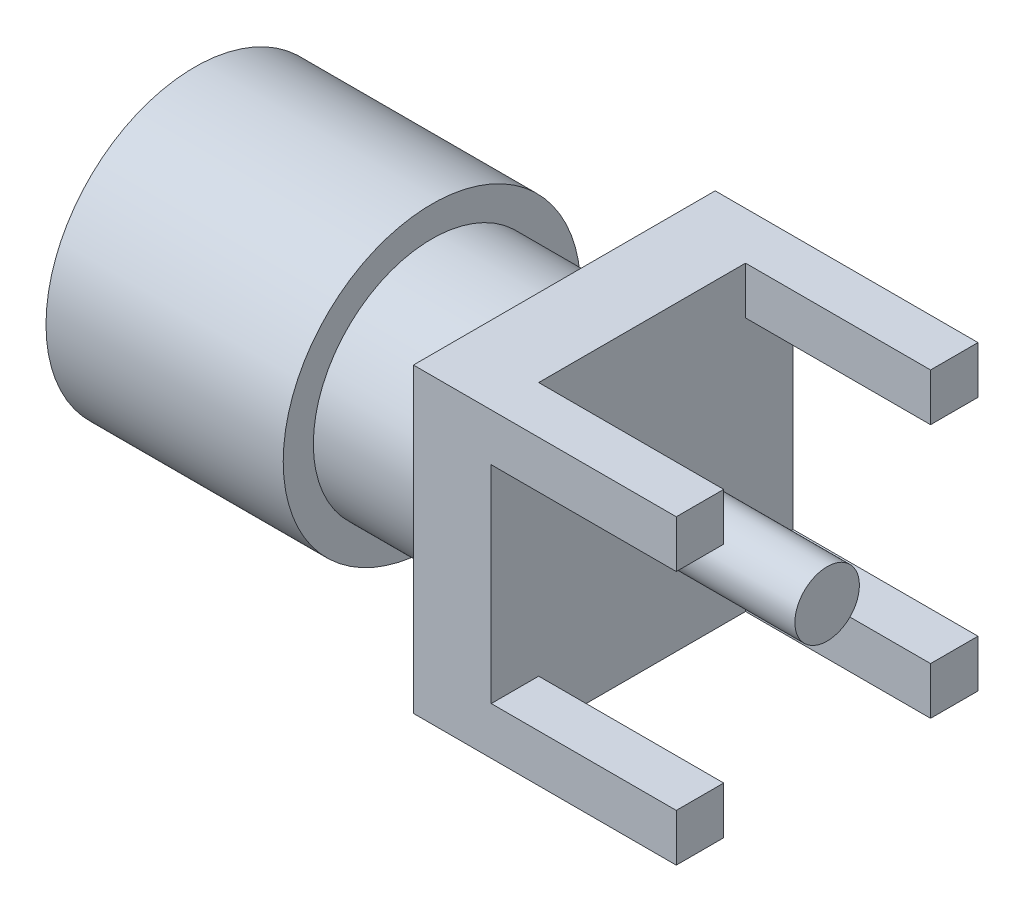
SolidWorks part; units mm, degrees
ref_plane "Front Plane" through (0, 0, 0) normal (0, 0, 1) x (1, 0, 0)
ref_plane "Top Plane" through (0, 0, 0) normal (0, 1, 0) x (1, 0, 0)
ref_plane "Right Plane" through (0, 0, 0) normal (1, 0, 0) x (0, 0, -1)
sketch "Sketch1" plane through (0, 0, 0) normal (0, 0, 1) x (1, 0, 0)
  line L0 (0, 54.8541) -> (0, -52.7238) construction
  line L1 (0, 0) -> (83.3995, 0) construction
  line L3 (-0.82, 3.18) -> (0.82, 3.18)
  line L4 (-0.82, 3.18) -> (-0.82, -3.18)
  line L5 (-0.82, -3.18) -> (0.82, -3.18)
  line L6 (0.82, 3.18) -> (0.82, -3.18)
  line L7 (-0.82, 3.18) -> (0.82, -3.18) construction
  line L8 (-0.82, -3.18) -> (0.82, 3.18) construction
  dimension "D1" = 6.36
  dimension "D2" = 1.64
extrude "Boss-Extrude1" add sketch "Sketch1" along normal blind 3.18 and the other way blind 3.18
sketch "Sketch2" plane through (-0.82, 0, 0) normal (-1, 0, 0) x (0, 0, 1)
  line L0 (-3.18, 3.18) -> (3.18, -3.18) construction
  line L1 (3.18, 3.18) -> (-3.18, -3.1272) construction
  line L2 (-3.18, 3.18) -> (-3.18, -3.18) construction
  circle A0 centre (0, 0) radius 2.5
  dimension "D1" = 5
extrude "Boss-Extrude2" add sketch "Sketch2" along normal blind 2.79
sketch "Sketch3" plane through (-3.61, 0, 0) normal (-1, 0, 0) x (0, 0, 1)
  circle A0 centre (0, 0) radius 3.135
  dimension "D1" = 6.27
extrude "Boss-Extrude3" add sketch "Sketch3" along normal blind 5
sketch "Sketch4" plane through (0.82, 0, 0) normal (1, 0, 0) x (0, 0, -1)
  line L1 (-3.18, 3.18) -> (-2.18, 3.18)
  line L2 (-3.18, 3.18) -> (-3.18, 2.18)
  line L3 (-3.18, 2.18) -> (-2.18, 2.18)
  line L4 (-2.18, 3.18) -> (-2.18, 2.18)
  line L5 (3.18, 3.18) -> (2.18, 3.18)
  line L6 (3.18, 3.18) -> (3.18, 2.18)
  line L7 (3.18, 2.18) -> (2.18, 2.18)
  line L8 (2.18, 3.18) -> (2.18, 2.18)
  line L9 (-3.18, -3.18) -> (-2.18, -3.18)
  line L10 (-3.18, -3.18) -> (-3.18, -2.18)
  line L11 (-3.18, -2.18) -> (-2.18, -2.18)
  line L12 (-2.18, -3.18) -> (-2.18, -2.18)
  line L13 (3.18, -3.18) -> (2.18, -3.18)
  line L14 (3.18, -3.18) -> (3.18, -2.18)
  line L15 (3.18, -2.18) -> (2.18, -2.18)
  line L16 (2.18, -3.18) -> (2.18, -2.18)
  dimension "D1" = 1
  dimension "D2" = 1
  dimension "D3" = 1
  dimension "D4" = 1
  dimension "D5" = 1
  dimension "D6" = 1
  dimension "D7" = 1
  dimension "D8" = 1
extrude "Boss-Extrude4" add sketch "Sketch4" along normal blind 3.9
sketch "Sketch5" plane through (0.82, 0, 0) normal (1, 0, 0) x (0, 0, -1)
  circle A0 centre (0, 0) radius 0.68
  dimension "D1" = 1.36
extrude "Boss-Extrude5" add sketch "Sketch5" along normal blind 3.9
sketch "Sketch6" plane through (-8.61, 0, 0) normal (-1, 0, 0) x (0, 0, 1)
  circle A0 centre (0, 0) radius 2.245
  dimension "D1" = 4.49
extrude "Cut-Extrude1" cut sketch "Sketch6" against normal blind 2
